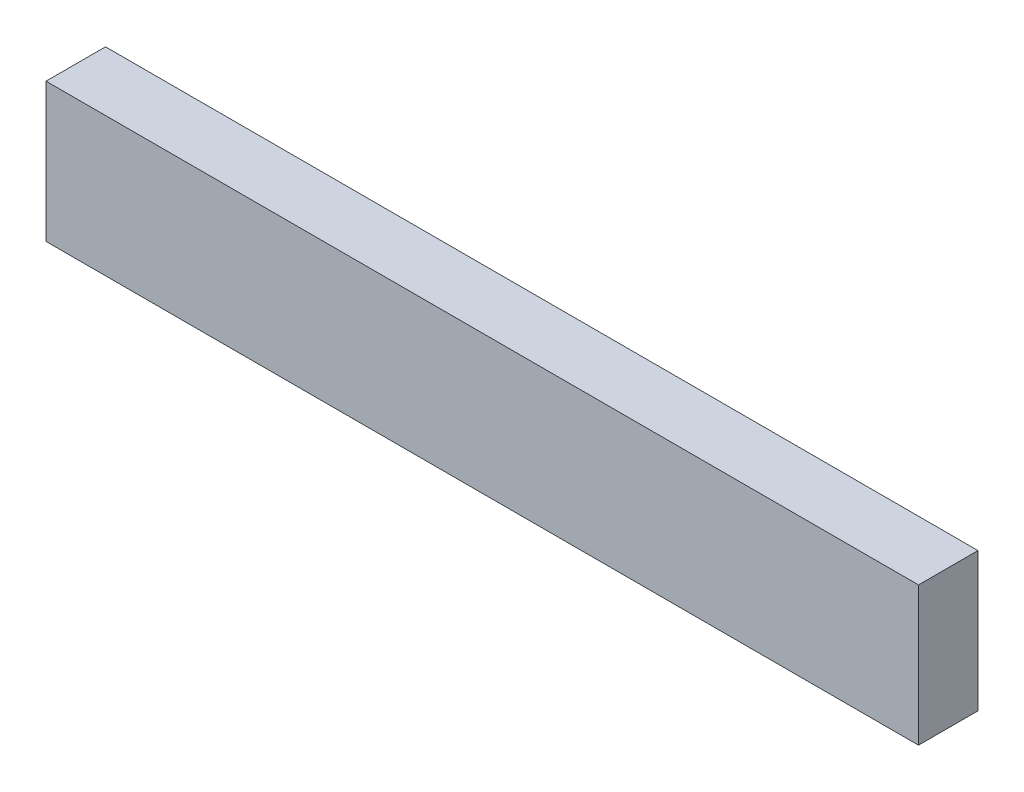
SolidWorks part; units mm, degrees
ref_plane "Front Plane" through (0, 0, 0) normal (0, 0, 1) x (1, 0, 0)
ref_plane "Top Plane" through (0, 0, 0) normal (0, 1, 0) x (1, 0, 0)
ref_plane "Right Plane" through (0, 0, 0) normal (1, 0, 0) x (0, 0, -1)
sketch "Sketch1" plane through (0, 0, 0) normal (1, 0, 0) x (0, 0, -1)
  line L1 (-19.05, -44.45) -> (19.05, -44.45)
  line L2 (-19.05, -44.45) -> (-19.05, 44.45)
  line L3 (-19.05, 44.45) -> (19.05, 44.45)
  line L4 (19.05, -44.45) -> (19.05, 44.45)
  line L5 (-19.05, -44.45) -> (19.05, 44.45) construction
  line L6 (-19.05, 44.45) -> (19.05, -44.45) construction
  point P0 (0, 0)
  dimension "D1" = 88.9
  dimension "D2" = 38.1
extrude "Boss-Extrude1" add sketch "Sketch1" along normal blind 558.8
